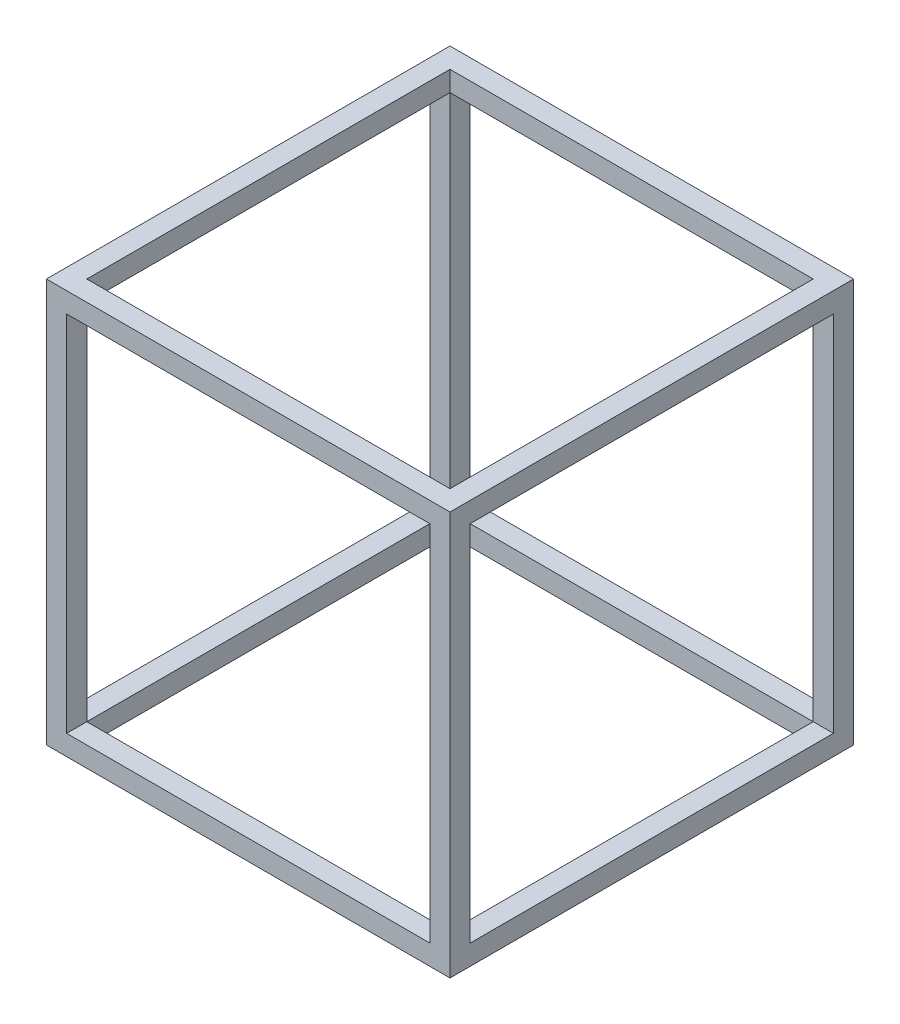
SolidWorks part; units mm, degrees
material "6063-T1"
ref_plane "Front Plane" through (0, 0, 0) normal (1, 0, 0) x (0, 1, 0)
ref_plane "Top Plane" through (0, 0, 0) normal (0, 0, 1) x (0, 1, 0)
ref_plane "Right Plane" through (0, 0, 0) normal (0, 1, 0) x (-1, 0, 0)
sketch "Sketch3" plane through (0, 0, 0) normal (0, 0, 1) x (0, 1, 0)
  line L0 (20, -20) -> (380, -20)
  line L1 (0, 0) -> (400, 0)
  line L2 (0, 0) -> (0, -400)
  line L3 (0, -400) -> (400, -400)
  line L4 (400, 0) -> (400, -400)
  line L5 (380, -20) -> (380, -380)
  line L6 (20, -380) -> (380, -380)
  line L7 (20, -20) -> (20, -380)
  line L8 (380, 0) -> (400, 0)
  line L9 (0, 0) -> (20, 0)
  line L10 (0, 0) -> (0, -20)
  line L11 (0, -20) -> (20, -20)
  line L12 (20, 0) -> (20, -20)
  line L13 (380, 0) -> (380, -20)
  line L14 (400, 0) -> (400, -20)
  line L15 (380, -20) -> (400, -20)
  line L16 (380, -380) -> (400, -380)
  line L17 (380, -380) -> (380, -400)
  line L18 (400, -380) -> (400, -400)
  line L19 (380, -400) -> (400, -400)
  line L20 (0, -380) -> (20, -380)
  line L21 (0, -380) -> (0, -400)
  line L22 (20, -380) -> (20, -400)
  line L23 (0, -400) -> (20, -400)
  line L24 (0, 0) -> (380, 0) construction
  dimension "D1" = 400
  dimension "500" = 400
  dimension "D6" = 380
  dimension "D3" = 20
  dimension "D4" = 2
  dimension "D5" = 2
extrude "Boss-Extrude4" add sketch "Sketch3" along normal blind 20 contours L13 L1 L12 L0 | L2 L20 L7 L11 | L6 L22 L3 L17 | L5 L16 L4 L15 region at (10, 200, 0) region at (200, 10, 0) region at (200, 390, 0) region at (390, 200, 0)
extrude "Boss-Extrude5" add sketch "Sketch3<5>" along normal blind 400 contours L22 L20 L2 L3 | L12 L1 L2 L11 | L13 L15 L4 L1 | L16 L17 L3 L4 region at (10, 10, 0) region at (10, 390, 0) region at (390, 10, 0) region at (390, 390, 0)
sketch "Sketch3<5>" plane through (0, 0, 0) normal (0, 0, 1) x (0, 1, 0) same geometry as "Sketch3"
pattern_linear "LPattern1" count 2 spacing 380 along (0, 0, 1) of "Boss-Extrude4"
equation "\"D3@LPattern1\"=\"frame_height\"-\"extrusion_width\""
equation "\"extrusion_width\"= 20mm'assuming we are using square beams"
equation "\"frame_height\"= 400mm'vertical height of the printer"
equation "\"500@Sketch3\"=\"frame_width\""
equation "\"frame_width\"= 400mm"
equation "\"frame_length\"= 400mm"
equation "\"D1@Sketch3\"=\"frame_length\""
equation "\"D3@Sketch3\"=\"extrusion_width\""
equation "\"D6@Sketch3\"=\"frame_length\"-\"extrusion_width\""
equation "\"D1@Boss-Extrude4\"=\"extrusion_width\""
equation "\"D1@Boss-Extrude5\"=\"frame_height\""
